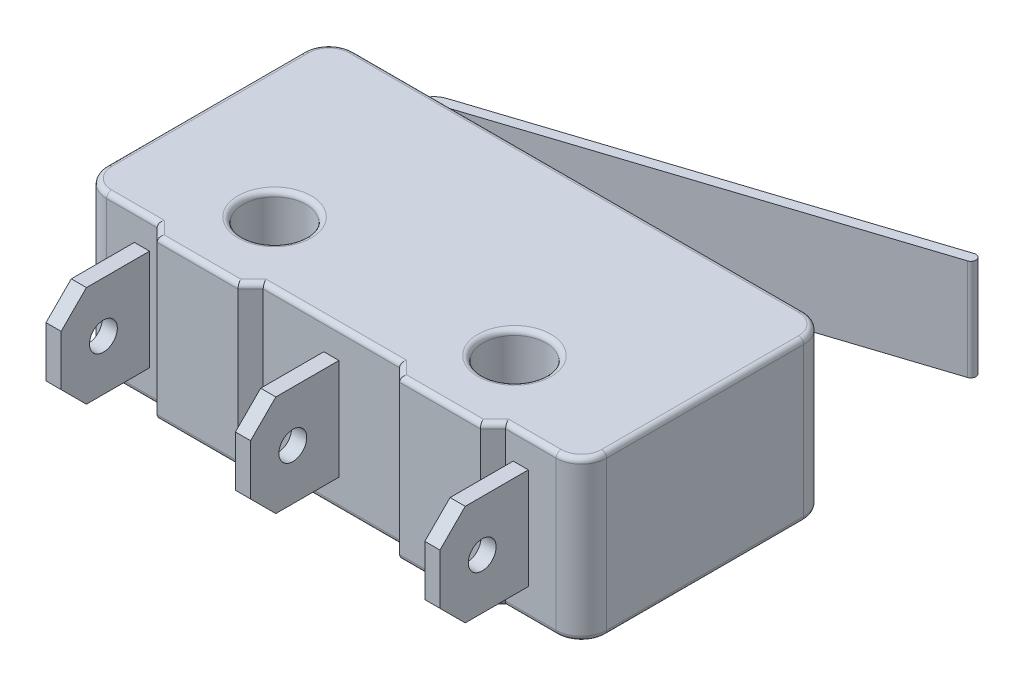
SolidWorks part; units mm, degrees
ref_plane "前视基准面" through (0, 0, 0) normal (0, 0, 1) x (1, 0, 0)
ref_plane "上视基准面" through (0, 0, 0) normal (0, 1, 0) x (1, 0, 0)
ref_plane "右视基准面" through (0, 0, 0) normal (1, 0, 0) x (0, 0, -1)
sketch "草图1" plane through (0, 0, 0) normal (0, 1, 0) x (1, 0, 0)
  line L0 (0, 43.2655) -> (0, -49.1255) construction
  line L1 (-57.2202, 0) -> (50.9404, 0) construction
  line L2 (-4.75, 43.2655) -> (-4.75, -49.1255) construction
  line L3 (4.75, 43.2655) -> (4.75, -49.1255) construction
  line L4 (-9.9, 6.3) -> (-9.9, -1.5)
  line L5 (9.9, 6.3) -> (9.9, -1.5)
  line L6 (-8.9, 7.3) -> (8.9, 7.3)
  line L7 (-6.4, -3) -> (-3.2, -3)
  line L8 (-2.7, -2.5) -> (2.7, -2.5)
  line L9 (2.7, -2.5) -> (3.2, -3)
  line L10 (-2.7, -2.5) -> (-3.2, -3)
  line L11 (-8.9, -2.5) -> (-6.9, -2.5)
  line L12 (-6.9, -2.5) -> (-6.4, -3)
  line L13 (6.4, -3) -> (6.9, -2.5)
  line L14 (6.9, -2.5) -> (8.9, -2.5)
  line L15 (-57.2202, -3) -> (50.9404, -3) construction
  line L16 (-9.9, 43.2655) -> (-9.9, -49.1255) construction
  line L17 (3.2, -3) -> (6.4, -3)
  line L18 (-57.2202, 7.3) -> (50.9404, 7.3) construction
  line L19 (9.9, 43.2655) -> (9.9, -49.1255) construction
  line L20 (-9.9, 7.3) -> (-9.9, -2.5)
  line L21 (-9.9, -2.5) -> (-6.9, -2.5)
  line L22 (-6.9, -2.5) -> (-6.4, -3)
  line L23 (-6.4, -3) -> (-3.2, -3)
  line L24 (-2.7, -2.5) -> (-3.2, -3)
  line L25 (-2.7, -2.5) -> (2.7, -2.5)
  line L26 (2.7, -2.5) -> (3.2, -3)
  line L27 (3.2, -3) -> (6.4, -3)
  line L28 (6.4, -3) -> (6.9, -2.5)
  line L29 (6.9, -2.5) -> (9.9, -2.5)
  line L30 (9.9, 7.3) -> (9.9, -2.5)
  line L31 (-9.9, 7.3) -> (9.9, 7.3)
  line L32 (-6.9, 7.3) -> (-6.9, -2.5) construction
  line L33 (-6.9, 7.3) -> (-6.9, 8.3) construction
  line L34 (-6.9, 8.3) -> (9.268, 13.5533) construction
  line L35 (-6.7, 7.3) -> (-6.7, 7.8641)
  line L36 (-6.4236, 8.2445) -> (9.3298, 13.3631)
  line L37 (-7.1, 7.3) -> (-7.1, 7.8641)
  line L38 (-6.5472, 8.6249) -> (9.2062, 13.7435)
  line L39 (-6.7, 7.3) -> (-6.7, 8.1547) construction
  line L40 (-6.7, 8.1547) -> (9.3298, 13.3631) construction
  line L41 (-7.1, 7.3) -> (-7.1, 8.4453) construction
  line L42 (-7.1, 8.4453) -> (9.2062, 13.7435) construction
  line L43 (-9.9, -2.5) -> (-6.9, -2.5) construction
  line L44 (-9.9, 7.3) -> (-9.9, -2.5) construction
  line L45 (6.9, -2.5) -> (9.9, -2.5) construction
  line L46 (9.9, 7.3) -> (9.9, -2.5) construction
  line L47 (-9.9, 7.3) -> (9.9, 7.3) construction
  line L48 (-7.5, -4.25) -> (7.5, -4.25) construction
  line L49 (-0.3, -6) -> (0.3, -6)
  line L50 (-0.3, -6) -> (-0.3, -2.5)
  line L51 (-0.3, -2.5) -> (0.3, -2.5)
  line L52 (0.3, -6) -> (0.3, -2.5)
  line L53 (-0.3, -6) -> (0.3, -2.5) construction
  line L54 (-0.3, -2.5) -> (0.3, -6) construction
  line L55 (-7.5, 43.2655) -> (-7.5, -49.1255) construction
  line L56 (7.5, 43.2655) -> (7.5, -49.1255) construction
  line L58 (-7.8, -6) -> (-7.2, -6)
  line L59 (-7.8, -6) -> (-7.8, -2.5)
  line L60 (-7.8, -2.5) -> (-7.2, -2.5)
  line L61 (-7.2, -6) -> (-7.2, -2.5)
  line L62 (-7.8, -6) -> (-7.2, -2.5) construction
  line L63 (-7.8, -2.5) -> (-7.2, -6) construction
  line L64 (7.2, -6) -> (7.8, -6)
  line L65 (7.2, -6) -> (7.2, -2.5)
  line L66 (7.2, -2.5) -> (7.8, -2.5)
  line L67 (7.8, -6) -> (7.8, -2.5)
  line L68 (7.2, -6) -> (7.8, -2.5) construction
  line L69 (7.2, -2.5) -> (7.8, -6) construction
  circle A0 centre (-4.75, 0) radius 1.25
  circle A1 centre (4.75, 0) radius 1.25
  arc A3 (9.3298, 13.3631) -> (9.2062, 13.7435) centre (9.268, 13.5533) ccw
  arc A4 (-6.7, 7.8641) -> (-6.4236, 8.2445) centre (-6.3, 7.8641) cw
  arc A5 (-7.1, 7.8641) -> (-6.5472, 8.6249) centre (-6.3, 7.8641) cw
  arc A6 (-8.9, -2.5) -> (-9.9, -1.5) centre (-8.9, -1.5) cw
  arc A7 (8.9, -2.5) -> (9.9, -1.5) centre (8.9, -1.5) ccw
  arc A8 (9.9, 6.3) -> (8.9, 7.3) centre (8.9, 6.3) ccw
  arc A9 (-8.9, 7.3) -> (-9.9, 6.3) centre (-8.9, 6.3) ccw
  arc A10 (-7.5, 43.2655) -> (7.5, 43.2655) centre (0, 43.2655) cw
  arc A11 (-7.5, -49.1255) -> (7.5, -49.1255) centre (0, -49.1255) ccw
  point P26 (0, -2.5)
  point P66 (-9.9, -2.5)
  point P70 (9.9, -2.5)
  point P77 (0, -4.25)
  dimension "D3" = 2.5
  dimension "D22" = 0.4
  dimension "D23" = 0.8
  dimension "D24" = 1
  dimension "D1" = 4.75
  dimension "D8" = 3
  dimension "D9" = 3
  dimension "D10" = 0.5
  dimension "D11" = 45
  dimension "D12" = 45
  dimension "D13" = 5.4
  dimension "D14" = 45
  dimension "D15" = 0
  dimension "D17" = 0.2
  dimension "D19" = 17
  dimension "D20" = 18
  dimension "D21" = 1
  dimension "D25" = 3.5
  dimension "D26" = 0.6
  dimension "D27" = 7.5
  dimension "D29" = 0.6
  dimension "D30" = 0.6
  dimension "D2" = 4.75
  dimension "D4" = 9.9
  dimension "D5" = 9.9
  dimension "D6" = 7.3
  dimension "D7" = 3
  dimension "D16" = 3
  dimension "D18" = 0.2
  dimension "D28" = 7.5
extrude "凸台-拉伸1" add sketch "草图1" along normal mid plane 6.3 contours L6 A9 L4 A6 L11 L21 L12 L7 L10 L8 L25 L9 L17 L13 L14 L29 A7 L5 A8 L31 A0 A1 region at (0, 0, -2.4243)
extrude "凸台-拉伸2" add sketch "草图1<3>" along normal mid plane 4 contours L58 L61 L21 L59 | L49 L52 L25 L50 | L64 L67 L29 L65 | A5 L37 L31 L35 A4 L36 A3 L38 region at (0.8601, 0, -10.7933) region at (-7.5, 0, 4.25) region at (7.5, 0, 4.25) region at (0, 0, 4.25)
sketch "草图1<3>" plane through (0, 0, 0) normal (0, 1, 0) x (1, 0, 0) same geometry as "草图1"
fillet "圆角1" radius 0.2 36 edges at (-7.9, -3.15, 2.5) (-9.6071, -3.15, 2.2071) (-9.9, -3.15, -2.4) (-9.6071, -3.15, -7.0071) (0, -3.15, -7.3) (9.6071, -3.15, -7.0071) (7.9, -3.15, 2.5) (9.6071, -3.15, 2.2071) (-7.9, 3.15, 2.5) (-9.6071, 3.15, 2.2071) (-9.9, 3.15, -2.4) (-9.6071, 3.15, -7.0071) (0, 3.15, -7.3) (9.6071, 3.15, -7.0071) (7.9, 3.15, 2.5) (9.6071, 3.15, 2.2071) (4.75, 3.15, 1.25) (-4.75, 3.15, 1.25) (6.65, 3.15, 2.75) (4.8, 3.15, 3) (2.95, 3.15, 2.75) (0, 3.15, 2.5) (-2.95, 3.15, 2.75) (-4.8, 3.15, 3) (-6.65, 3.15, 2.75) (-6.65, -3.15, 2.75) (-4.8, -3.15, 3) (-2.95, -3.15, 2.75) (6.65, -3.15, 2.75) (4.8, -3.15, 3) (2.95, -3.15, 2.75) (0, -3.15, 2.5) (-4.75, -3.15, 1.25) (4.75, -3.15, 1.25) (9.9, -3.15, -2.4) (9.9, 3.15, -2.4)
chamfer "倒角1" distance 1 angle 45 6 edges at (-7.5, -2, 6) (0, -2, 6) (7.5, -2, 6) (7.5, 2, 6) (0, 2, 6) (-7.5, 2, 6)
sketch "草图2" plane through (7.8, 0, 0) normal (1, 0, 0) x (0, 0, -1)
  circle A0 centre (-4.3282, 0) radius 0.5515
  dimension "D1" = 1.103
extrude "切除-拉伸1" cut sketch "草图2" against normal through all
